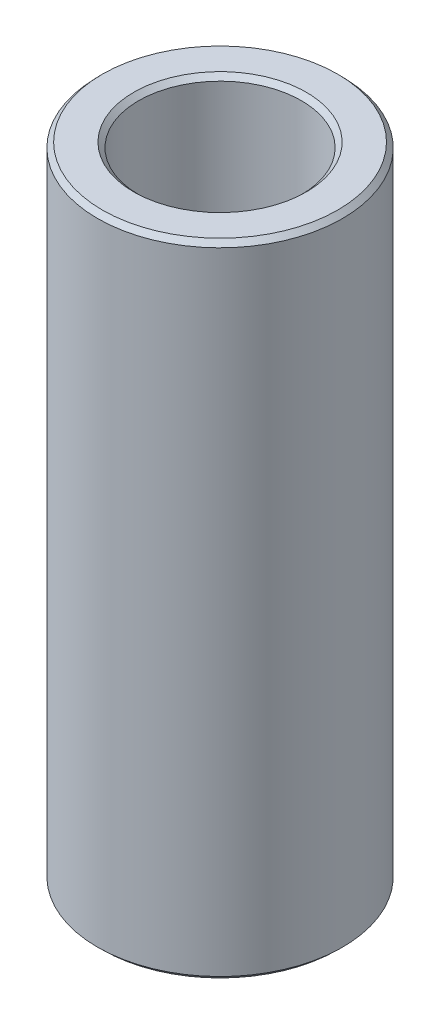
SolidWorks part; units mm, degrees
ref_plane "Front Plane" through (0, 0, 0) normal (0, 0, 1) x (1, 0, 0)
ref_plane "Top Plane" through (0, 0, 0) normal (0, 1, 0) x (1, 0, 0)
ref_plane "Right Plane" through (0, 0, 0) normal (1, 0, 0) x (0, 0, -1)
sketch "Sketch1" plane through (0, 0, 0) normal (0, 1, 0) x (1, 0, 0)
  circle A0 centre (0, 0) radius 15
  dimension "SLEEVE_OD" = 30
extrude "Boss-Extrude1" add sketch "Sketch1" along normal blind 78.4855
sketch "Sketch2" plane through (0, 0, 0) normal (0, 1, 0) x (1, 0, 0)
  circle A0 centre (0, 0) radius 9.9696
  dimension "BORE_D" = 19.9393
extrude "Cut-Extrude1" cut sketch "Sketch2" along normal through all
chamfer "Chamfer1" distance 0.6071 angle 43.884 4 edges at (0, 78.4855, 9.9696) (0, 0, 9.9696) (0, 0, 15) (0, 78.4855, 15) first distance on face at (0, 78.4855, 9.9696) first distance on face at (0, 0, 9.9696) first distance on face at (0, 78.4855, 15)
